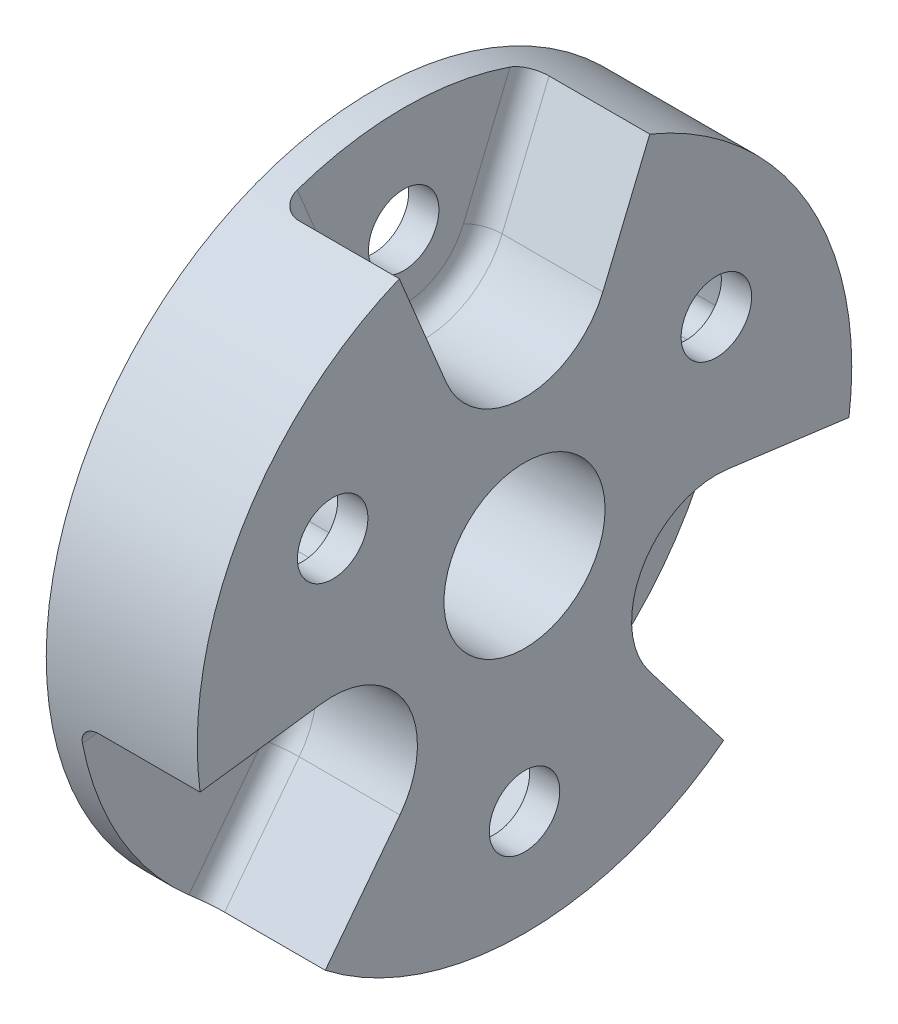
SolidWorks part; units mm, degrees
ref_plane "Front Plane" through (0, 0, 0) normal (0, 0, 1) x (1, 0, 0)
ref_plane "Top Plane" through (0, 0, 0) normal (0, 1, 0) x (1, 0, 0)
ref_plane "Right Plane" through (0, 0, 0) normal (1, 0, 0) x (0, 0, -1)
sketch "Sketch1" plane through (0, 0, 0) normal (1, 0, 0) x (0, 0, -1)
  circle A0 centre (0, 0) radius 32.5
  dimension "D1" = 65
extrude "Boss-Extrude1" add sketch "Sketch1" along normal blind 15
sketch "Sketch2" plane through (15, 0, 0) normal (1, 0, 0) x (0, 0, -1)
  line L0 (-12.4372, 30.0261) -> (-7.7782, 18.7782)
  line L1 (7.7782, 18.7782) -> (12.4372, 30.0261)
  line L2 (0, 0) -> (0, 22) construction
  line L3 (12.3733, -16.1252) -> (19.7847, -25.784)
  line L4 (32.222, -4.2421) -> (20.1515, -2.653)
  line L5 (-20.1515, -2.653) -> (-32.222, -4.2421)
  line L6 (-19.7847, -25.784) -> (-12.3733, -16.1252)
  line L7 (-29.4876, -0.8562) -> (-10.884, 1.593)
  line L8 (-6.8216, 8.6294) -> (-14.0023, 25.9651)
  line L9 (10.884, 1.593) -> (29.4876, -0.8562)
  line L10 (14.0023, 25.9651) -> (6.8216, 8.6294)
  line L11 (-4.0625, -10.2223) -> (-15.4853, -25.1089)
  line L12 (15.4853, -25.1089) -> (4.0625, -10.2223)
  line L14 (-7.7782, 18.7782) -> (0, 0) construction
  line L15 (0, 0) -> (7.7782, 18.7782) construction
  circle A0 centre (0, 0) radius 32.5 construction
  arc A1 (-7.7782, 18.7782) -> (7.7782, 18.7782) centre (0, 22) ccw
  circle A2 centre (0, 0) radius 22 construction
  circle A3 centre (0, 22) radius 3.5
  circle A4 centre (0, 0) radius 8
  circle A5 centre (19.0526, 11) radius 3.5
  arc A10 (20.1515, -2.653) -> (12.3733, -16.1252) centre (19.0526, -11) ccw
  circle A11 centre (19.0526, -11) radius 3.5
  circle A12 centre (0, 0) radius 29.5
  circle A13 centre (0, -22) radius 3.5
  circle A14 centre (-19.0526, -11) radius 3.5
  circle A15 centre (-19.0526, 11) radius 3.5
  arc A16 (-12.3733, -16.1252) -> (-20.1515, -2.653) centre (-19.0526, -11) ccw
  arc A17 (-10.884, 1.593) -> (-6.8216, 8.6294) centre (0, 0) cw
  arc A18 (6.8216, 8.6294) -> (10.884, 1.593) centre (0, 0) cw
  arc A19 (4.0625, -10.2223) -> (-4.0625, -10.2223) centre (0, 0) cw
  point P28 (0, 0)
  point P33 (0, 0)
  point P36 (0, 0)
  point P51 (0, 0)
  circle M13 centre (0, 0) radius 32.5
  dimension "D2" = 44
  dimension "D3" = 7
  dimension "D4" = 16
  dimension "D8" = 3
  dimension "D9" = 45
  dimension "D11" = 3
  dimension "D1" = 45
  dimension "D10" = 3
  dimension "D7" = 3
  dimension "D6" = 3
  dimension "D5" = 6
  dimension "D12" = 3
extrude "Cut-Extrude1" cut sketch "Sketch2" against normal offset from surface (12 mm away) 3 contours L1 A12 L0 A1 A3 | A12 L1 L0 M13 | L3 A12 L4 A10 A11 | A12 L3 L4 M13 | L6 A16 L5 A12 A14 | A12 L5 L6 M13 region at (15, 30.2329, 0) region at (15, 29.2237, 0) region at (15, -15.1165, 26.1825) region at (15, -3.5287, 24.6631) region at (15, -15.1165, -26.1825) region at (15, -14.6104, -25.3059) up to face at (0, 0, -32.5)
extrude "Cut-Extrude2" cut sketch "Sketch2<3>" against normal through all contours A3 | A14 | A15 | A13 | A4 | A11 | A5 region at (15, 22, 0) region at (15, 0, 0) region at (15, 11, -19.0526) region at (15, -11, -19.0526) region at (15, -22, 0) region at (15, -11, 19.0526) region at (15, 11, 19.0526)
sketch "Sketch2<3>" plane through (15, 0, 0) normal (1, 0, 0) x (0, 0, -1) same geometry as "Sketch2"
extrude "Cut-Extrude3" cut sketch "Sketch2<4>" along normal offset from surface (12 mm away) 3 from surface contours L7 A17 L8 A12 A15 | L10 A18 L9 A12 A5 | L12 A19 L11 A12 A13 region at (15, 17.1628, 10.7364) region at (15, 14.9392, -25.0294) region at (15, -17.8877, 9.4845) up to face at (15, 11, 15.5526) starting at face at (0, 22, -3.5)
sketch "Sketch2<4>" plane through (15, 0, 0) normal (1, 0, 0) x (0, 0, -1) same geometry as "Sketch2"
fillet "Fillet1" radius 2 9 edges at (3, -20.9546, -16.079) (3, -3.4475, -26.1867) (3, -3.4475, 26.1867) (3, -20.9546, 16.079) (3, 24.4021, 10.1077) (3, 13.581, 0) (3, -6.7905, -11.7615) (3, -6.7905, 11.7615) (3, 24.4021, -10.1077)
fillet "Fillet2" radius 2 24 edges at (12, -29.5, 0) (6, -25.1089, 15.4853) (6, -25.1089, -15.4853) (12, -17.6656, -9.7739) (12, -17.6656, 9.7739) (12, -11, 0) (6, -10.2223, 4.0625) (6, -10.2223, -4.0625) (6, -0.8562, 29.4876) (12, 0.3684, 20.1858) (6, 1.593, 10.884) (6, 8.6294, 6.8216) (12, 5.5, 9.5263) (12, 14.75, 25.5477) (12, 17.2972, 10.4119) (6, 25.9651, 14.0023) (6, -0.8562, -29.4876) (12, 0.3684, -20.1858) (6, 1.593, -10.884) (12, 5.5, -9.5263) (6, 8.6294, -6.8216) (12, 17.2972, -10.4119) (12, 14.75, -25.5477) (6, 25.9651, -14.0023)
